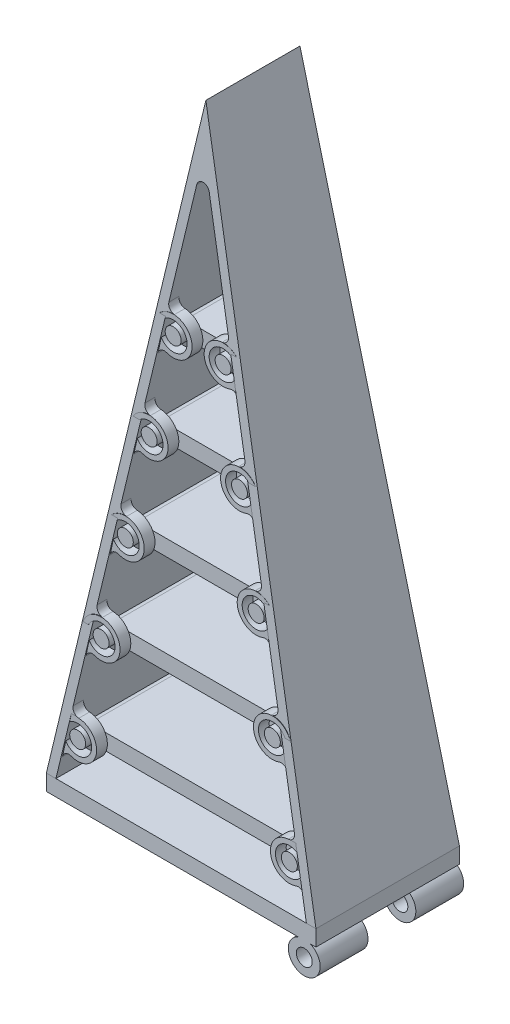
SolidWorks part; units mm, degrees
ref_plane "Ebene vorne" through (0, 0, 0) normal (0, 0, 1) x (1, 0, 0)
ref_plane "Ebene oben" through (0, 0, 0) normal (0, 1, 0) x (1, 0, 0)
ref_plane "Ebene rechts" through (0, 0, 0) normal (1, 0, 0) x (0, 0, -1)
ref_plane "Ebene7" through (0, 0, 9) normal (0, 0, 1) x (1, 0, 0)
sketch "Skizze1" plane through (0, 0, 0) normal (0, 0, 1) x (1, 0, 0)
  line L0 (0, 0) -> (16.9111, -80)
  line L1 (16.9111, -80) -> (15.7111, -80)
  line L2 (15.7111, -80) -> (0, -5.6767)
  line L3 (0, -5.6767) -> (-15.7111, -80)
  line L4 (-15.7111, -80) -> (-16.9111, -80)
  line L5 (-16.9111, -80) -> (0, 0)
  point P2 (-16.3111, -80)
  dimension "D1" = 1.2
  dimension "D2" = 1.2
  dimension "D3" = 23.872
  dimension "D4" = 80
extrude "Aufsatz-Linear austragen4" add sketch "Skizze1" along normal blind 18
ref_plane "Ebene8" through (17, 0, 0) normal (1, 0, 0) x (0, 0, -1)
sketch "Skizze11" plane through (17, 0, 0) normal (1, 0, 0) x (0, 0, -1)
  line L0 (-18, -80) -> (-14.9, 0)
  line L1 (-18, 0) -> (0, 0) construction
  line L2 (-14.9, 0) -> (-18, 0)
  line L3 (-18, 0) -> (-18, -80)
  line L4 (0, -80) -> (-3.1, 0)
  line L5 (-3.1, 0) -> (0, 0)
  line L6 (0, 0) -> (0, -80)
  dimension "D1" = 3.1
  dimension "D2" = 3.1
extrude "Schnitt-Linear austragen1" cut sketch "Skizze11" against normal through all
sketch "Skizze6" plane through (0, 0, 9) normal (0, 0, 1) x (1, 0, 0)
  line L1 (0, -5.6767) -> (-15.7111, -80) construction
  line L2 (15.7111, -80) -> (0, -5.6767) construction
  line L8 (3.1325, -25.6767) -> (-3.1325, -25.6767)
  line L11 (-3.1325, -27.6767) -> (3.1325, -27.6767)
  arc A0 (-3.1325, -25.6767) -> (-3.1325, -27.6767) centre (-3.1325, -26.6767) ccw
  arc A1 (3.1325, -25.6767) -> (3.1325, -27.6767) centre (3.1325, -26.6767) cw
  point P4 (-4.1325, -26.6767)
  point P9 (4.1325, -26.6767)
  dimension "D3" = 0.3
  dimension "D1" = 20
  dimension "D2" = 2
  dimension "D4" = 0.3
extrude "Aufsatz-Linear austragen5" add sketch "Skizze6" along normal blind 5.37 and the other way blind 5.37
sketch "Skizze7" plane through (0, 0, 9) normal (0, 0, 1) x (1, 0, 0)
  line L9 (5.6692, -37.6767) -> (-5.6692, -37.6767)
  line L12 (-5.6692, -39.6767) -> (5.6692, -39.6767)
  line L13 (-3.1325, -27.6767) -> (3.1325, -27.6767) construction
  line L14 (0, -5.6767) -> (-15.7111, -80) construction
  line L15 (15.7111, -80) -> (0, -5.6767) construction
  arc A0 (-5.6692, -37.6767) -> (-5.6692, -39.6767) centre (-5.6692, -38.6767) ccw
  arc A1 (5.6692, -37.6767) -> (5.6692, -39.6767) centre (5.6692, -38.6767) cw
  point P3 (-6.6692, -38.6767)
  point P10 (6.6692, -38.6767)
  dimension "D3" = 0.3
  dimension "D1" = 10
  dimension "D2" = 2
  dimension "D4" = 0.3
extrude "Aufsatz-Linear austragen6" add sketch "Skizze7" along normal blind 5.85 and the other way blind 5.85
sketch "Skizze8" plane through (0, 0, 9) normal (0, 0, 1) x (1, 0, 0)
  line L9 (8.2059, -49.6767) -> (-8.2059, -49.6767)
  line L12 (-8.2059, -51.6767) -> (8.2059, -51.6767)
  line L13 (-5.6692, -39.6767) -> (5.6692, -39.6767) construction
  line L14 (0, -5.6767) -> (-15.7111, -80) construction
  line L15 (15.7111, -80) -> (0, -5.6767) construction
  arc A0 (-8.2059, -49.6767) -> (-8.2059, -51.6767) centre (-8.2059, -50.6767) ccw
  arc A1 (8.2059, -49.6767) -> (8.2059, -51.6767) centre (8.2059, -50.6767) cw
  point P6 (-9.2059, -50.6767)
  point P11 (9.2059, -50.6767)
  dimension "D3" = 0.3
  dimension "D1" = 10
  dimension "D2" = 2
  dimension "D4" = 0.3
extrude "Aufsatz-Linear austragen7" add sketch "Skizze8" along normal blind 6.3 and the other way blind 6.3
sketch "Skizze9" plane through (0, 0, 9) normal (0, 0, 1) x (1, 0, 0)
  line L9 (10.7426, -61.6767) -> (-10.7426, -61.6767)
  line L12 (-10.7426, -63.6767) -> (10.7426, -63.6767)
  line L13 (-8.2059, -51.6767) -> (8.2059, -51.6767) construction
  line L14 (0, -5.6767) -> (-15.7111, -80) construction
  line L15 (15.7111, -80) -> (0, -5.6767) construction
  arc A0 (-10.7426, -61.6767) -> (-10.7426, -63.6767) centre (-10.7426, -62.6767) ccw
  arc A1 (10.7426, -61.6767) -> (10.7426, -63.6767) centre (10.7426, -62.6767) cw
  point P3 (-11.7426, -62.6767)
  point P10 (11.7426, -62.6767)
  dimension "D3" = 0.3
  dimension "D1" = 10
  dimension "D2" = 2
  dimension "D4" = 0.3
extrude "Aufsatz-Linear austragen8" add sketch "Skizze9" along normal blind 6.8 and the other way blind 6.8
sketch "Skizze10" plane through (0, 0, 9) normal (0, 0, 1) x (1, 0, 0)
  line L9 (13.2792, -73.6767) -> (-13.2792, -73.6767)
  line L12 (-13.2792, -75.6767) -> (13.2792, -75.6767)
  line L13 (-10.7426, -63.6767) -> (10.7426, -63.6767) construction
  line L14 (0, -5.6767) -> (-15.7111, -80) construction
  line L15 (15.7111, -80) -> (0, -5.6767) construction
  arc A0 (-13.2792, -73.6767) -> (-13.2792, -75.6767) centre (-13.2792, -74.6767) ccw
  arc A1 (13.2792, -73.6767) -> (13.2792, -75.6767) centre (13.2792, -74.6767) cw
  point P3 (-14.2792, -74.6767)
  point P10 (14.2792, -74.6767)
  dimension "D3" = 0.3
  dimension "D1" = 10
  dimension "D2" = 2
  dimension "D4" = 0.3
extrude "Aufsatz-Linear austragen9" add sketch "Skizze10" along normal blind 7.2 and the other way blind 7.2
sketch "Skizze13" plane through (0, 0, 14.37) normal (0, 0, 1) x (1, 0, 0)
  circle A0 centre (-3.1325, -26.6767) radius 1
  circle A1 centre (3.1325, -26.6767) radius 1
  dimension "D1" = 2
  dimension "D2" = 2
extrude "Aufsatz-Linear austragen12" add sketch "Skizze13" along normal blind 1.5
sketch "Skizze14" plane through (0, 0, 14.85) normal (0, 0, 1) x (1, 0, 0)
  circle A0 centre (-5.6692, -38.6767) radius 1
  circle A1 centre (5.6692, -38.6767) radius 1
extrude "Aufsatz-Linear austragen13" add sketch "Skizze14" along normal blind 1.5
sketch "Skizze15" plane through (0, 0, 15.3) normal (0, 0, 1) x (1, 0, 0)
  circle A0 centre (-8.2059, -50.6767) radius 1
  circle A1 centre (8.2059, -50.6767) radius 1
extrude "Aufsatz-Linear austragen14" add sketch "Skizze15" along normal blind 1.5
sketch "Skizze16" plane through (0, 0, 15.8) normal (0, 0, 1) x (1, 0, 0)
  circle A0 centre (-10.7426, -62.6767) radius 1
  circle A1 centre (10.7426, -62.6767) radius 1
extrude "Aufsatz-Linear austragen15" add sketch "Skizze16" along normal blind 1.5
sketch "Skizze17" plane through (0, 0, 16.2) normal (0, 0, 1) x (1, 0, 0)
  circle A0 centre (-13.2792, -74.6767) radius 1
  circle A1 centre (13.2792, -74.6767) radius 1
extrude "Aufsatz-Linear austragen16" add sketch "Skizze17" along normal blind 1.5
sketch "Skizze18" plane through (0, 0, 3.63) normal (0, 0, -1) x (-1, 0, 0)
  circle A0 centre (-3.1325, -26.6767) radius 1
  circle A1 centre (3.1325, -26.6767) radius 1
extrude "Aufsatz-Linear austragen17" add sketch "Skizze18" along normal blind 1.5
sketch "Skizze19" plane through (0, 0, 3.15) normal (0, 0, -1) x (-1, 0, 0)
  circle A0 centre (-5.6692, -38.6767) radius 1
  circle A1 centre (5.6692, -38.6767) radius 1
extrude "Aufsatz-Linear austragen18" add sketch "Skizze19" along normal blind 1.5
sketch "Skizze20" plane through (0, 0, 2.7) normal (0, 0, -1) x (-1, 0, 0)
  circle A0 centre (-8.2059, -50.6767) radius 1
  circle A1 centre (8.2059, -50.6767) radius 1
extrude "Aufsatz-Linear austragen19" add sketch "Skizze20" along normal blind 1.5
sketch "Skizze21" plane through (0, 0, 2.2) normal (0, 0, -1) x (-1, 0, 0)
  circle A0 centre (-10.7426, -62.6767) radius 1
  circle A1 centre (10.7426, -62.6767) radius 1
extrude "Aufsatz-Linear austragen20" add sketch "Skizze21" along normal blind 1.5
sketch "Skizze22" plane through (0, 0, 1.8) normal (0, 0, -1) x (-1, 0, 0)
  circle A0 centre (-13.2792, -74.6767) radius 1
  circle A1 centre (13.2792, -74.6767) radius 1
extrude "Aufsatz-Linear austragen21" add sketch "Skizze22" along normal blind 1.5
sketch "Skizze24" plane through (0, 0, 15.87) normal (0, 0, 1) x (1, 0, 0)
  circle A0 centre (-3.1325, -26.6767) radius 1.75
  circle A1 centre (-3.1325, -26.6767) radius 2.375
  circle A2 centre (3.1325, -26.6767) radius 1.75
  circle A3 centre (3.1325, -26.6767) radius 2.375
  dimension "D1" = 3.5
  dimension "D2" = 4.75
  dimension "D3" = 3.5
  dimension "D4" = 4.75
extrude "Aufsatz-Linear austragen22" add sketch "Skizze24" against normal blind 1.35
sketch "Skizze25" plane through (0, 0, 16.35) normal (0, 0, 1) x (1, 0, 0)
  circle A0 centre (-5.6692, -38.6767) radius 1.75
  circle A1 centre (-5.6692, -38.6767) radius 2.375
  circle A2 centre (5.6692, -38.6767) radius 1.75
  circle A3 centre (5.6692, -38.6767) radius 2.375
  dimension "D1" = 3.5
  dimension "D2" = 4.75
  dimension "D3" = 3.5
  dimension "D4" = 4.75
extrude "Aufsatz-Linear austragen23" add sketch "Skizze25" against normal blind 1.35
sketch "Skizze26" plane through (0, 0, 16.8) normal (0, 0, 1) x (1, 0, 0)
  circle A0 centre (-8.2059, -50.6767) radius 1.75
  circle A1 centre (-8.2059, -50.6767) radius 2.375
  circle A2 centre (8.2059, -50.6767) radius 1.75
  circle A3 centre (8.2059, -50.6767) radius 2.375
  dimension "D1" = 3.5
  dimension "D2" = 4.75
  dimension "D3" = 3.5
  dimension "D4" = 4.75
extrude "Aufsatz-Linear austragen24" add sketch "Skizze26" against normal blind 1.35
sketch "Skizze27" plane through (0, 0, 17.3) normal (0, 0, 1) x (1, 0, 0)
  circle A0 centre (-10.7426, -62.6767) radius 1.75
  circle A1 centre (-10.7426, -62.6767) radius 2.375
  circle A2 centre (10.7426, -62.6767) radius 1.75
  circle A3 centre (10.7426, -62.6767) radius 2.375
  dimension "D1" = 3.5
  dimension "D2" = 4.75
  dimension "D3" = 3.5
  dimension "D4" = 4.75
extrude "Aufsatz-Linear austragen25" add sketch "Skizze27" against normal blind 1.35
sketch "Skizze28" plane through (0, 0, 17.7) normal (0, 0, 1) x (1, 0, 0)
  circle A0 centre (-13.2792, -74.6767) radius 1.75
  circle A1 centre (-13.2792, -74.6767) radius 2.375
  circle A2 centre (13.2792, -74.6767) radius 1.75
  circle A3 centre (13.2792, -74.6767) radius 2.375
  dimension "D1" = 3.5
  dimension "D2" = 4.75
  dimension "D3" = 3.5
  dimension "D4" = 4.75
extrude "Aufsatz-Linear austragen26" add sketch "Skizze28" against normal blind 1.35
sketch "Skizze29" plane through (0, 0, 2.13) normal (0, 0, -1) x (-1, 0, 0)
  circle A0 centre (-3.1325, -26.6767) radius 1.75
  circle A1 centre (-3.1325, -26.6767) radius 2.375
  circle A2 centre (3.1325, -26.6767) radius 1.75
  circle A3 centre (3.1325, -26.6767) radius 2.375
extrude "Aufsatz-Linear austragen27" add sketch "Skizze29" against normal blind 1.35
sketch "Skizze30" plane through (0, 0, 1.65) normal (0, 0, -1) x (-1, 0, 0)
  circle A0 centre (-5.6692, -38.6767) radius 1.75
  circle A1 centre (-5.6692, -38.6767) radius 2.375
  circle A2 centre (5.6692, -38.6767) radius 1.75
  circle A3 centre (5.6692, -38.6767) radius 2.375
extrude "Aufsatz-Linear austragen28" add sketch "Skizze30" against normal blind 1.35
sketch "Skizze31" plane through (0, 0, 1.2) normal (0, 0, -1) x (-1, 0, 0)
  circle A0 centre (-8.2059, -50.6767) radius 1.75
  circle A1 centre (-8.2059, -50.6767) radius 2.375
  circle A2 centre (8.2059, -50.6767) radius 1.75
  circle A3 centre (8.2059, -50.6767) radius 2.375
extrude "Aufsatz-Linear austragen29" add sketch "Skizze31" against normal blind 1.35
sketch "Skizze32" plane through (0, 0, 0.7) normal (0, 0, -1) x (-1, 0, 0)
  circle A0 centre (-10.7426, -62.6767) radius 1.75
  circle A1 centre (-10.7426, -62.6767) radius 2.375
  circle A2 centre (10.7426, -62.6767) radius 1.75
  circle A3 centre (10.7426, -62.6767) radius 2.375
extrude "Aufsatz-Linear austragen30" add sketch "Skizze32" against normal blind 1.35
sketch "Skizze33" plane through (0, 0, 0.3) normal (0, 0, -1) x (-1, 0, 0)
  circle A0 centre (-13.2792, -74.6767) radius 1.75
  circle A1 centre (-13.2792, -74.6767) radius 2.375
  circle A2 centre (13.2792, -74.6767) radius 1.75
  circle A3 centre (13.2792, -74.6767) radius 2.375
extrude "Aufsatz-Linear austragen31" add sketch "Skizze33" against normal blind 1.35
fillet "Verrundung1" radius 0.8 1 edges at (0, -5.6767, 9)
fillet "Verrundung2" radius 0.8 40 edges at (12.4073, -64.3707, 16.625) (9.8706, -52.3707, 16.125) (7.3339, -40.3707, 15.675) (4.7973, -28.3707, 15.195) (-4.7973, -28.3707, 15.195) (-7.3339, -40.3707, 15.675) (-9.8706, -52.3707, 16.125) (-12.4073, -64.3707, 16.625) (-14.9439, -76.3707, 17.025) (14.9439, -76.3707, 17.025) (14.116, -72.454, 17.025) (-14.116, -72.454, 17.025) (-11.5793, -60.454, 16.5963) (11.5793, -60.454, 16.5963) (9.0427, -48.454, 16.1138) (-9.0427, -48.454, 16.1138) (-6.506, -36.454, 15.6563) (6.506, -36.454, 15.6563) (3.9693, -24.454, 15.1838) (-3.9693, -24.454, 15.1838) (-7.3339, -40.3707, 2.325) (-4.7973, -28.3707, 2.805) (-3.9693, -24.454, 2.8162) (-6.506, -36.454, 2.3437) (-9.0427, -48.454, 1.8862) (-9.8706, -52.3707, 1.875) (-12.4073, -64.3707, 1.375) (-11.5793, -60.454, 1.4037) (-14.116, -72.454, 0.975) (-14.9439, -76.3707, 0.975) (14.9439, -76.3707, 0.975) (14.116, -72.454, 0.975) (12.4073, -64.3707, 1.375) (11.5793, -60.454, 1.4037) (9.8706, -52.3707, 1.875) (9.0427, -48.454, 1.8862) (7.3339, -40.3707, 2.325) (6.506, -36.454, 2.3437) (4.7973, -28.3707, 2.805) (3.9693, -24.454, 2.8162)
sketch "Skizze37" plane through (0, -80, 0) normal (0, -1, 0) x (1, 0, 0)
  line L0 (-16.9111, 0) -> (-15.7111, 0)
  line L1 (-15.7111, 0) -> (16.9111, 0)
  line L2 (16.9111, 0) -> (16.9111, 18)
  line L3 (16.9111, 18) -> (-16.9111, 18)
  line L4 (-16.9111, 18) -> (-16.9111, 0)
extrude "Aufsatz-Linear austragen32" add sketch "Skizze37" along normal blind 2
sketch "Skizze38" plane through (0, 0, 18) normal (0, 0, 1) x (1, 0, 0)
  circle A0 centre (15.4414, -83.854) radius 2
extrude "Aufsatz-Linear austragen33" add sketch "Skizze38" against normal blind 18
sketch "Skizze39" plane through (0, 0, 18) normal (0, 0, 1) x (1, 0, 0)
  circle A0 centre (15.4414, -83.854) radius 1
extrude "Schnitt-Linear austragen2" cut sketch "Skizze39" against normal blind 18
sketch "Skizze40" plane through (0, 0, 18) normal (0, 0, 1) x (1, 0, 0)
  circle A0 centre (15.4414, -83.854) radius 2
extrude "Schnitt-Linear austragen3" cut sketch "Skizze40" against normal blind 6 from offset 6 offset against normal yes
sketch "Skizze42" plane through (0, -82, 0) normal (0, -1, 0) x (1, 0, 0)
  circle A0 centre (-14.5497, 9.2939) radius 0.5
  point P2 (-14.5497, 9.6923)
extrude "Schnitt-Linear austragen4" cut sketch "Skizze42" against normal blind 2
sketch "Skizze43" plane through (0, -82, 0) normal (0, -1, 0) x (1, 0, 0)
  line L1 (-13.9679, 8.351) -> (11.3804, 8.351)
  line L2 (-13.9679, 8.351) -> (-13.9679, 10.3734)
  line L3 (-13.9679, 10.3734) -> (11.3804, 10.3734)
  line L4 (11.3804, 8.351) -> (11.3804, 10.3734)
  point P4 (-13.9679, 8.351)
extrude "Aufsatz-Linear austragen34" add sketch "Skizze43" along normal blind 2
fillet "Verrundung3" radius 1 1 edges at (-13.9679, -84, 9.3622)
sketch "Skizze44" plane through (11.3804, 0, 0) normal (1, 0, 0) x (0, 0, -1)
  line L0 (-8.351, -84) -> (-10.3734, -84) construction
  circle A0 centre (-9.3622, -84) radius 0.6176
extrude "Schnitt-Linear austragen5" cut sketch "Skizze44" against normal blind 32
sketch "Skizze45" plane through (0, -84, 0) normal (0, -1, 0) x (1, 0, 0)
  line L1 (11.3804, 10.3734) -> (-12.9679, 10.3734) construction
  line L2 (-12.9679, 8.351) -> (11.3804, 8.351) construction
  line L6 (-12.9679, 10.3734) -> (-12.9679, 8.351)
  line L7 (-12.9679, 8.351) -> (-11.9659, 8.351)
  line L8 (-11.9659, 8.351) -> (-11.9659, 10.3734)
  line L9 (-11.9659, 10.3734) -> (-12.9679, 10.3734)
  line L10 (9.2026, 8.351) -> (9.2026, 10.3734)
  line L11 (9.2026, 10.3734) -> (8.5252, 10.3734)
  line L12 (8.5252, 10.3734) -> (8.5252, 8.351)
  line L13 (8.5252, 8.351) -> (9.2026, 8.351)
extrude "Aufsatz-Linear austragen35" add sketch "Skizze45" along normal blind 0.5
